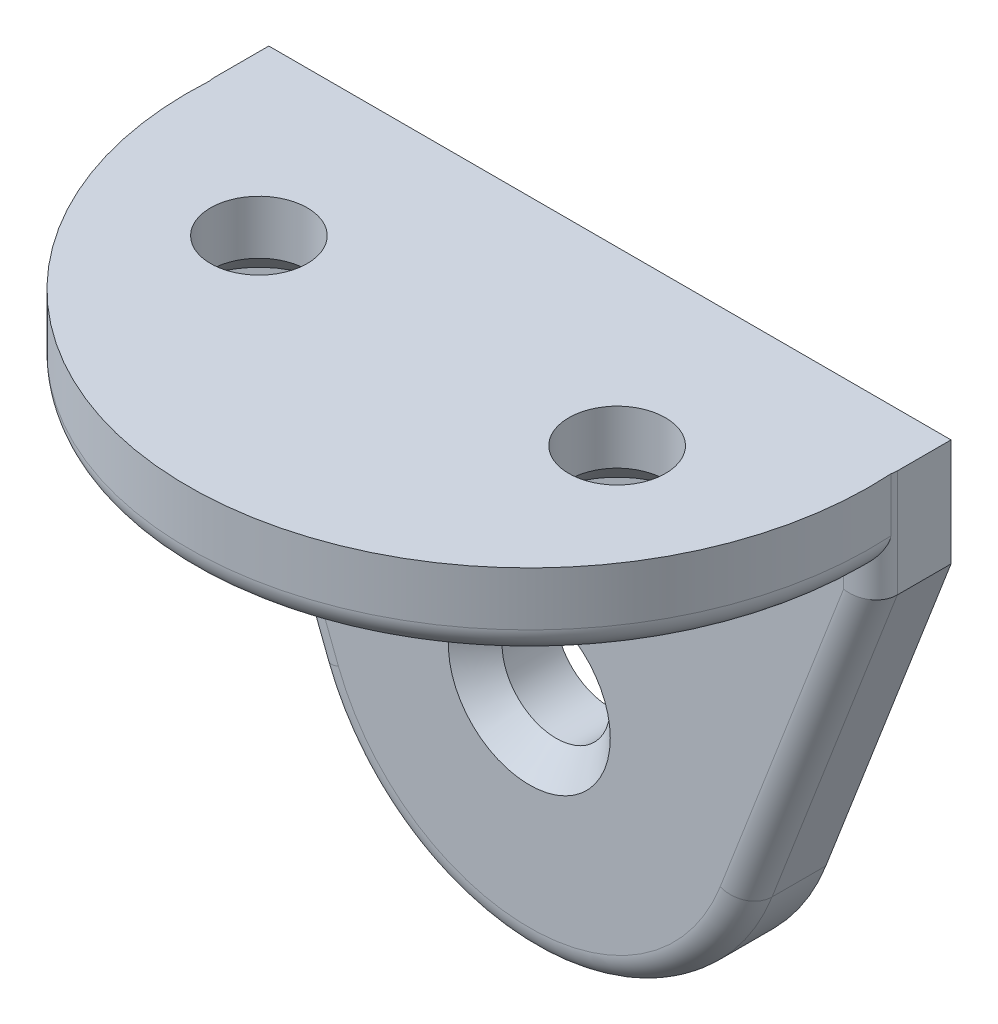
SolidWorks part; units mm, degrees
ref_plane "Front Plane" through (0, 0, 0) normal (0, 0, 1) x (1, 0, 0)
ref_plane "Top Plane" through (0, 0, 0) normal (0, 1, 0) x (1, 0, 0)
ref_plane "Right Plane" through (0, 0, 0) normal (1, 0, 0) x (0, 0, -1)
sketch "Sketch1" plane through (0, 0, 0) normal (0, 0, 1) x (1, 0, 0)
  line L0 (12.7, 349.2472) -> (-12.7, 349.2472)
  line L1 (-101.65, 349.2472) -> (101.55, 349.2472) construction
  line L2 (-12.7, 1143) -> (-12.7, 0) construction
  line L3 (-12.7, 349.2472) -> (-12.7, 345.2472)
  line L4 (12.7, 349.2472) -> (12.7, 345.2472)
  line L5 (12.7, 1143) -> (12.7, 0) construction
  line L6 (-12.7, 345.2472) -> (-8.0393, 333.1805)
  line L7 (12.7, 345.2472) -> (8.0393, 333.1805)
  arc A2 (-8.0393, 333.1805) -> (8.0393, 333.1805) centre (0, 336.2857) ccw
  circle A3 centre (0, 336.2857) radius 2.0138
  dimension "D3" = 8.6181
  dimension "D4" = 4.0275
  dimension "D1" = 4
  dimension "D2" = 25.4
  dimension "D5" = 12.9615
extrude "Boss-Extrude1" add sketch "Sketch1" along normal blind 3
sketch "Sketch2" plane through (0, 349.2472, 0) normal (0, -1, 0) x (1, 0, 0)
  line L0 (12.7, 3) -> (-12.7, 3) construction
  line L1 (-12.7, 3) -> (12.7, 3)
  arc A0 (12.7, 3) -> (-12.7, 3) centre (0, 3) ccw
  circle A1 centre (-6.7684, 6.3) radius 1.8
  circle A2 centre (6.6684, 6.4) radius 1.8
extrude "Boss-Extrude2" add sketch "Sketch2" along normal blind 3
chamfer "Chamfer1" distance 1 angle 45 3 edges at (2.0138, 336.2857, 3) (6.6684, 346.2472, 4.6) (-6.7684, 346.2472, 4.5)
fillet "Fillet1" radius 1 1 edges at (0, 346.2472, 15.7)
fillet "Fillet2" radius 1 5 edges at (-12.7, 346.2472, 3) (12.7, 346.2472, 3) (-10.3696, 339.2139, 3) (10.3697, 339.2139, 3) (0, 327.6675, 3)
